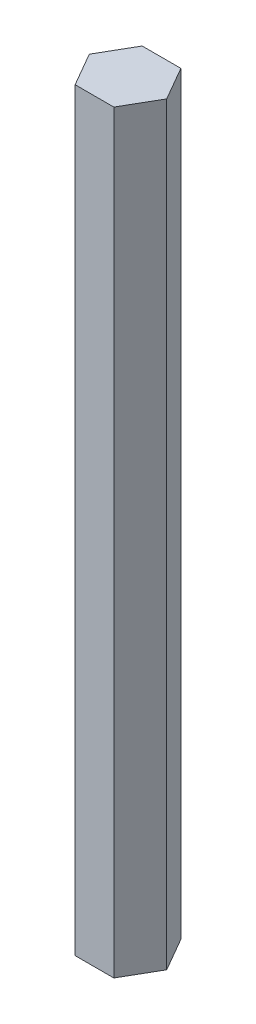
SolidWorks part; units mm, degrees
material "6061-T6 (SS)"
ref_plane "Front" through (0, 0, 0) normal (0, 0, 1) x (1, 0, 0)
ref_plane "Top" through (0, 0, 0) normal (0, 1, 0) x (1, 0, 0)
ref_plane "Right" through (0, 0, 0) normal (1, 0, 0) x (0, 0, -1)
sketch "Sketch1" plane through (0, 0, 0) normal (0, 1, 0) x (1, 0, 0)
  line L1 (7.3323, 0) -> (3.6662, 6.35)
  line L2 (3.6662, 6.35) -> (-3.6662, 6.35)
  line L3 (-3.6662, 6.35) -> (-7.3323, 0)
  line L4 (-7.3323, 0) -> (-3.6662, -6.35)
  line L5 (-3.6662, -6.35) -> (3.6662, -6.35)
  line L6 (3.6662, -6.35) -> (7.3323, 0)
  circle A0 centre (0, 0) radius 6.35 construction
  dimension "D1" = 12.7
extrude "Boss-Extrude1" add sketch "Sketch1" along normal blind 142.875
ref_axis "Axis1" through (0, 50, 0) along (0, -1, 0)
